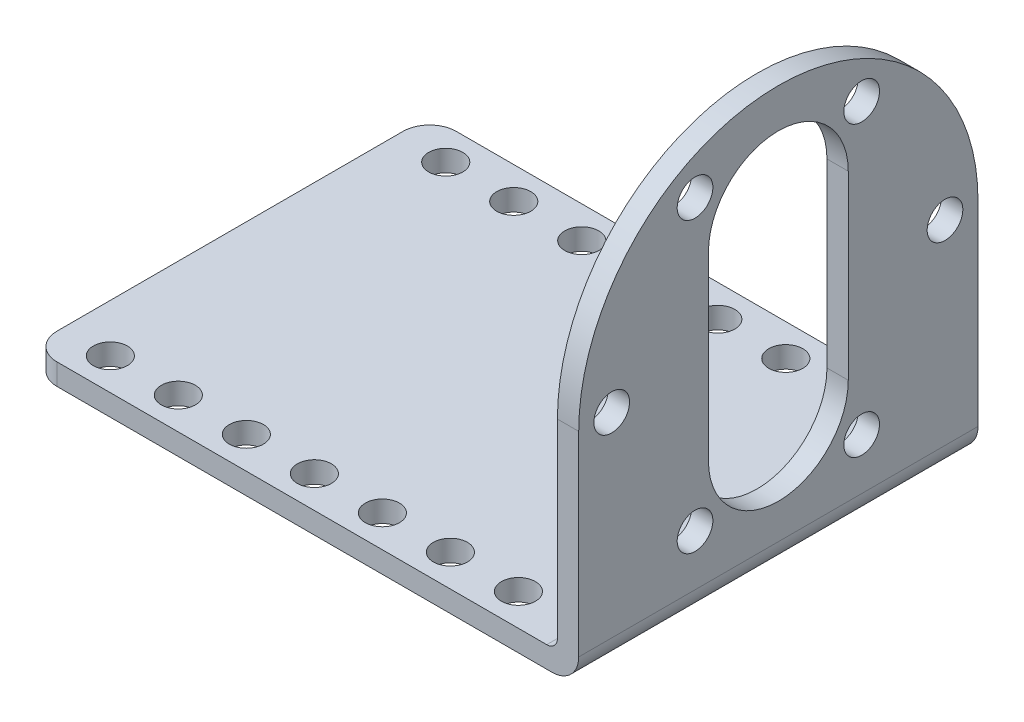
SolidWorks part; units mm, degrees
material "1060 Alloy"
ref_plane "Front Plane" through (0, 0, 0) normal (0, 0, 1) x (1, 0, 0)
ref_plane "Top Plane" through (0, 0, 0) normal (0, 1, 0) x (1, 0, 0)
ref_plane "Right Plane" through (0, 0, 0) normal (1, 0, 0) x (0, 0, -1)
sketch "Sketch1" plane through (0, 0, 0) normal (1, 0, 0) x (0, 0, -1)
  line L0 (-766.126, 0) -> (37540.1761, 0) construction
  line L1 (0, -766.126) -> (0, 37540.1761) construction
  line L2 (18.75, 0) -> (-18.75, 0)
  line L3 (-18.75, 0) -> (-18.75, 39.6)
  line L4 (18.75, 0) -> (18.75, 39.6)
  line L5 (-1000, 20.85) -> (49000, 20.85) construction
  line L6 (-6.565, 29.35) -> (-6.565, 12.35)
  line L7 (6.565, 29.35) -> (6.565, 12.35)
  arc A0 (18.75, 20.85) -> (-18.75, 20.85) centre (0, 20.85) ccw
  circle A1 centre (0, 20.85) radius 15.65 construction
  circle A2 centre (-15.65, 20.85) radius 1.675
  circle A3 centre (-7.825, 34.4033) radius 1.675
  circle A4 centre (7.825, 34.4033) radius 1.675
  circle A5 centre (15.65, 20.85) radius 1.675
  circle A6 centre (7.825, 7.2967) radius 1.675
  circle A7 centre (-7.825, 7.2967) radius 1.675
  circle A8 centre (0, 29.35) radius 6.565
  circle A10 centre (0, 12.35) radius 6.565
  point P18 (0, 0)
  point P31 (0, 20.85)
  dimension "D4" = 31.3
  dimension "D5" = 3.35
  dimension "D7" = 13.13
  dimension "D1" = 18.75
  dimension "D2" = 39.6
  dimension "D3" = 20.85
  dimension "D8" = 8.5
  dimension "D6" = 6
extrude "Boss-Extrude1" add sketch "Sketch1" along normal blind 2 contours L4 A0 L3 L2 A7 A6 A5 A4 A3 A2 L7 A10 L6 A8 region at (0, 0.5454, 0)
sketch "Sketch2" plane through (0, 0, 0) normal (0, 1, 0) x (1, 0, 0)
  line L0 (-1000, 0) -> (49000, 0) construction
  line L1 (0, -18.75) -> (0, 18.75)
  line L2 (0, 18.75) -> (-49.5, 18.75)
  line L3 (-49.5, 18.75) -> (-49.5, -18.75)
  line L4 (0, -18.75) -> (-49.5, -18.75)
  line L5 (2, -18.75) -> (2, 18.75) construction
  circle A0 centre (-44.9875, 15.75) radius 1.6
  circle A1 centre (-38.6, 15.75) radius 1.6
  circle A2 centre (-32.2125, 15.75) radius 1.6
  circle A3 centre (-25.825, 15.75) radius 1.6
  circle A4 centre (-19.4375, 15.75) radius 1.6
  circle A5 centre (-13.05, 15.75) radius 1.6
  circle A6 centre (-6.6625, 15.75) radius 1.6
  circle A7 centre (-6.6625, -15.75) radius 1.6
  circle A8 centre (-13.05, -15.75) radius 1.6
  circle A9 centre (-19.4375, -15.75) radius 1.6
  circle A10 centre (-44.9875, -15.75) radius 1.6
  circle A11 centre (-38.6, -15.75) radius 1.6
  circle A12 centre (-32.2125, -15.75) radius 1.6
  circle A13 centre (-25.825, -15.75) radius 1.6
  point P9 (0, 0)
  point P10 (-49.5, 0)
  dimension "D2" = 3.2
  dimension "D1" = 49.5
  dimension "D3" = 15.05
  dimension "D4" = 15.75
  dimension "D6" = 25.55
  dimension "D5" = 7
extrude "Boss-Extrude2" add sketch "Sketch2" along normal blind 2
fillet "Fillet1" radius 2.5 3 edges at (2, 0, 0) (-49.5, 1, -18.75) (-49.5, 1, 18.75)
fillet "Fillet2" radius 1 1 edges at (0, 2, 0)
